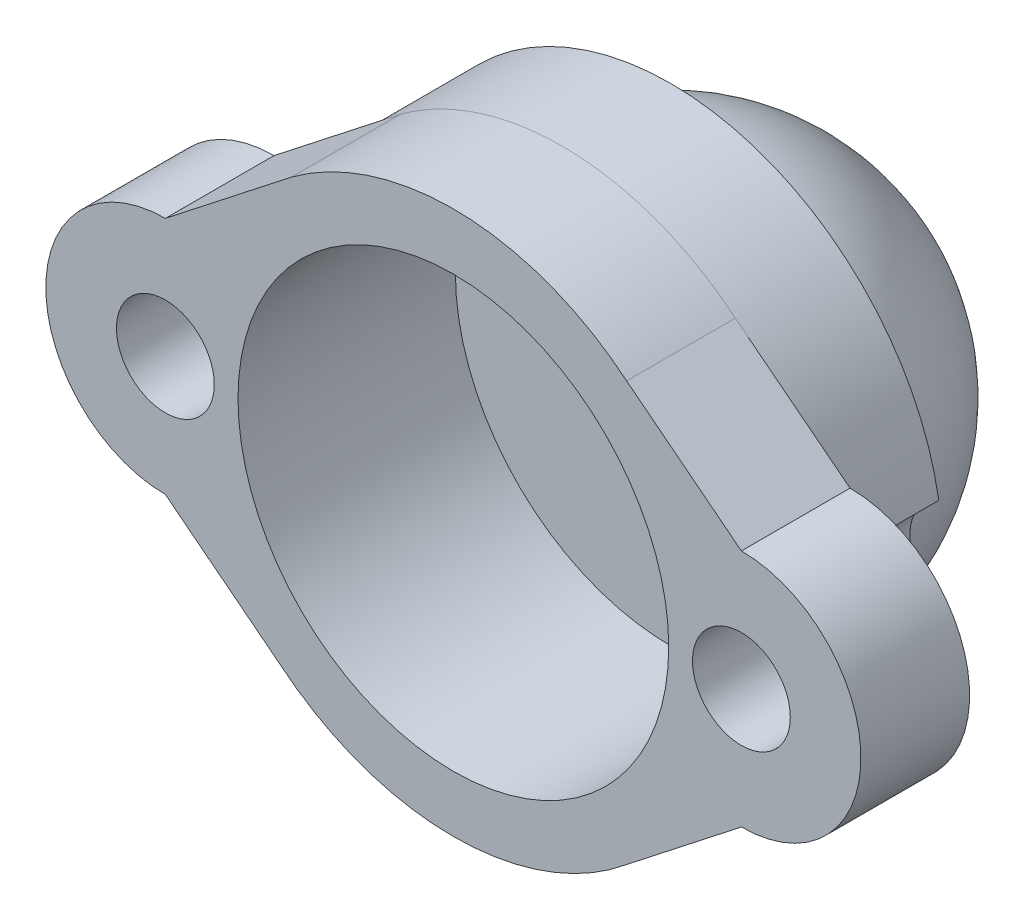
SolidWorks part; units mm, degrees
ref_plane "Front Plane" through (0, 0, 0) normal (0, 0, 1) x (1, 0, 0)
ref_plane "Top Plane" through (0, 0, 0) normal (0, 1, 0) x (1, 0, 0)
ref_plane "Right Plane" through (0, 0, 0) normal (1, 0, 0) x (0, 0, -1)
sketch "Sketch1" plane through (0, 0, 0) normal (0, 0, 1) x (1, 0, 0)
  line L0 (-8.3681, 2.7656) -> (-8.3681, -9.9344) construction
  line L1 (-8.3681, -9.9344) -> (10.6819, -9.9344) construction
  line L2 (10.6819, -9.9344) -> (10.6819, 2.7656) construction
  line L3 (10.6819, 2.7656) -> (-8.3681, 2.7656) construction
  line L4 (-8.3681, -3.5844) -> (10.6819, -3.5844) construction
  line L5 (-5.5741, -0.7904) -> (-2.5309, 1.593)
  line L6 (-5.5741, -6.3784) -> (-2.6418, -8.675)
  line L7 (7.8879, -0.7904) -> (5.2066, 1.3097)
  line L8 (7.8879, -6.3784) -> (5.1904, -8.4912)
  circle A0 centre (1.1569, -3.5844) radius 5.033
  circle A1 centre (-5.5741, -3.5844) radius 1.143
  circle A2 centre (7.8879, -3.5844) radius 1.143
  arc A3 (-2.7585, -8.5836) -> (1.1569, -9.9344) centre (1.1569, -3.5844) ccw
  arc A4 (-5.5741, -0.7904) -> (-5.5741, -6.3784) centre (-5.5741, -3.5844) ccw
  arc A5 (7.8879, -6.3784) -> (7.8879, -0.7904) centre (7.8879, -3.5844) ccw
  arc A6 (1.1569, 2.7656) -> (-2.7585, 1.4148) centre (1.1569, -3.5844) ccw
  arc A7 (7.4228, -2.5403) -> (-5.1089, -2.5403) centre (1.1569, -3.5844) ccw
  arc A8 (-5.1089, -4.6285) -> (7.4228, -4.6285) centre (1.1569, -3.5844) ccw
  dimension "D5" = 2.286
  dimension "D6" = 2.286
  dimension "D7" = 13.462
  dimension "D8" = 2.794
  dimension "D9" = 12.7
  dimension "D1" = 19.05
  dimension "D2" = 12.7
extrude "Boss-Extrude1" add sketch "Sketch1" along normal blind 2.54 contours A8 A1 A7 L5 A4 L6 | A8 L8 A5 L7 A7 A2 | A1 A8 A2 A7 L5 A0 region at (-4.1642, 0.1713, 0) region at (-2.7155, 1.2217, 0) region at (6.4781, 0.1713, 0)
sketch "Sketch2" plane through (0, 0, 0) normal (0, 0, -1) x (-1, 0, 0)
  arc A0 (5.1068, -2.5413) -> (-7.4207, -2.5413) centre (-1.1569, -3.5844) ccw
  circle A1 centre (-1.1569, -3.5844) radius 5.033 construction
  circle A2 centre (-1.1569, -3.5844) radius 5.033
  arc A3 (-7.4207, -4.6275) -> (-7.4207, -2.5413) centre (-7.8879, -3.5844) ccw
  arc A4 (5.1068, -2.5413) -> (5.1068, -4.6275) centre (5.5741, -3.5844) ccw
  arc A5 (-7.4207, -4.6275) -> (5.1068, -4.6275) centre (-1.1569, -3.5844) ccw
  dimension "D1" = 0
  dimension "D2" = 12.7
extrude "Boss-Extrude2" add sketch "Sketch2" along normal blind 2.54
ref_axis "Axis1" through (1.1569, -3.5844, 2.54) along (0, 0, -1)
ref_plane "Plane1" through (1.1569, 0, 0) normal (1, 0, 0) x (0, 0, -1)
sketch "Sketch5" plane through (1.1569, 0, 0) normal (1, 0, 0) x (0, 0, -1)
  line L0 (-2.54, -3.5844) -> (2.54, -3.5844) construction
  line L1 (2.54, -8.6174) -> (2.54, 1.4486) construction
  line L2 (2.54, -3.5844) -> (7.62, -3.5844)
  line L4 (2.54, -3.5844) -> (2.54, 1.4956)
  arc A0 (7.62, -3.5844) -> (2.54, 1.4956) centre (2.54, -3.5844) ccw
  dimension "D1" = 10.16
  dimension "D2" = 0
  dimension "D3" = 0
revolve "Revolve1" add sketch "Sketch5" angle 360 about L2
